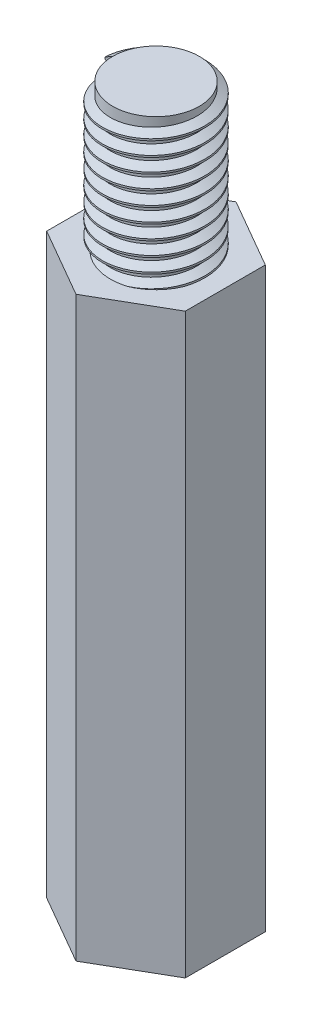
SolidWorks part; units mm, degrees
ref_plane "Front Plane" through (0, 0, 0) normal (0, 0, 1) x (1, 0, 0)
ref_plane "Top Plane" through (0, 0, 0) normal (0, 1, 0) x (1, 0, 0)
ref_plane "Right Plane" through (0, 0, 0) normal (1, 0, 0) x (0, 0, -1)
sketch "Sketch1" plane through (0, 0, 0) normal (0, 1, 0) x (1, 0, 0)
  line L1 (2.4, 1.3856) -> (0, 2.7713)
  line L2 (0, 2.7713) -> (-2.4, 1.3856)
  line L3 (-2.4, 1.3856) -> (-2.4, -1.3856)
  line L4 (-2.4, -1.3856) -> (0, -2.7713)
  line L5 (0, -2.7713) -> (2.4, -1.3856)
  line L6 (2.4, -1.3856) -> (2.4, 1.3856)
  circle A0 centre (0, 0) radius 2.4 construction
  circle A1 centre (0, 0) radius 1.25
  dimension "D1" = 4.8
  dimension "D2" = 2.5
extrude "Boss-Extrude1" add sketch "Sketch1" along normal blind 5
thread "Thread1" pitch 0.5 method cut profile "Thread Profile1" start angle 0, offset 2, length 22, pitch 0.5, diameter 2.5
ref_plane "Plane1" through (-1.25, 7, 0) normal (0, 0, 1) x (-1, 0, 0)
sketch "Thread Profile1" plane through (-1.25, 7, 0) normal (0, 0, 1) x (-1, 0, 0)
  line L0 (0, 0) -> (0, 0.5) construction
  line L1 (0, 0) -> (0.2706, 0.1562)
  line L2 (0.2706, 0.1562) -> (0.2706, 0.2187)
  line L3 (0.2706, 0.2187) -> (0, 0.375)
  line L4 (0.2706, 0.1875) -> (0, 0.1875) construction
  line L11 (0, 0) -> (0, 0.375)
  point P2 (0, 0)
  dimension "Pitch" = 0.5
  dimension "Profile_Angle" = 60
  dimension "Profile_Land" = 0.0625
  dimension "Profile_Height" = 0.2706
sketch "Sketch2" plane through (0, 5, 0) normal (0, 1, 0) x (1, 0, 0)
  line L6 (2.4, -1.3856) -> (2.4, 1.3856)
  line L7 (2.4, 1.3856) -> (0, 2.7713)
  line L8 (0, 2.7713) -> (-2.4, 1.3856)
  line L9 (-2.4, 1.3856) -> (-2.4, -1.3856)
  line L10 (-2.4, -1.3856) -> (0, -2.7713)
  line L11 (0, -2.7713) -> (2.4, -1.3856)
  line L12 (2.4, -1.3856) -> (2.4, 1.3856)
  line L13 (2.4, 1.3856) -> (0, 2.7713)
  line L14 (0, 2.7713) -> (-2.4, 1.3856)
  line L15 (-2.4, 1.3856) -> (-2.4, -1.3856)
  line L16 (-2.4, -1.3856) -> (0, -2.7713)
  line L17 (0, -2.7713) -> (2.4, -1.3856)
  dimension "D1" = 0
extrude "Boss-Extrude2" add sketch "Sketch2" along normal blind 15
sketch "Sketch3" plane through (0, 20, 0) normal (0, 1, 0) x (1, 0, 0)
  circle A0 centre (0, 0) radius 1.5
  dimension "D1" = 3
extrude "Boss-Extrude3" add sketch "Sketch3" along normal blind 5
thread "Thread2" pitch 0.5 method extrude profile "Thread Profile2" start angle 0, offset 0, length 10, pitch 0.5, diameter 3
ref_plane "Plane2" through (-1.5, 25, 0) normal (0, 0, 1) x (-1, 0, 0)
sketch "Thread Profile2" plane through (-1.5, 25, 0) normal (0, 0, 1) x (-1, 0, 0)
  line L0 (0, 0) -> (0, 0.5) construction
  line L1 (0, 0) -> (0.2706, 0.1562)
  line L2 (0.2706, 0.1562) -> (0.2706, 0.2187)
  line L3 (0.2706, 0.2187) -> (0, 0.375)
  line L4 (0.2706, 0.1875) -> (0, 0.1875) construction
  line L11 (0, 0) -> (0, 0.375)
  point P2 (0, 0)
  dimension "Pitch" = 0.5
  dimension "Profile_Angle" = 60
  dimension "Profile_Land" = 0.0625
  dimension "Profile_Height" = 0.2706
